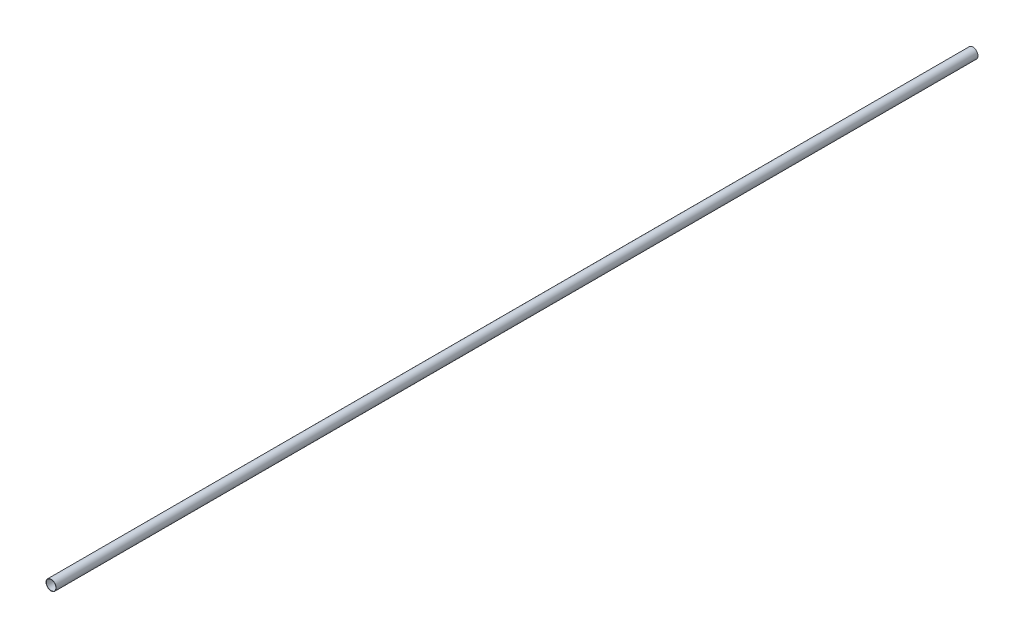
SolidWorks part; units mm, degrees
material "6061-T6 (SS)"
ref_plane "Front Plane" through (0, 0, 0) normal (0, 0, 1) x (1, 0, 0)
ref_plane "Top Plane" through (0, 0, 0) normal (0, 1, 0) x (1, 0, 0)
ref_plane "Right Plane" through (0, 0, 0) normal (1, 0, 0) x (0, 0, -1)
sketch "Sketch1" plane through (0, 0, 0) normal (0, 0, 1) x (1, 0, 0)
  circle A0 centre (-116.373, -116.373) radius 4.318
  circle A1 centre (-116.373, -116.373) radius 4.572
  dimension "D1" = 0.254
  dimension "D2" = 8.636
extrude "Boss-Extrude1" add sketch "Sketch1" along normal blind 825.5
